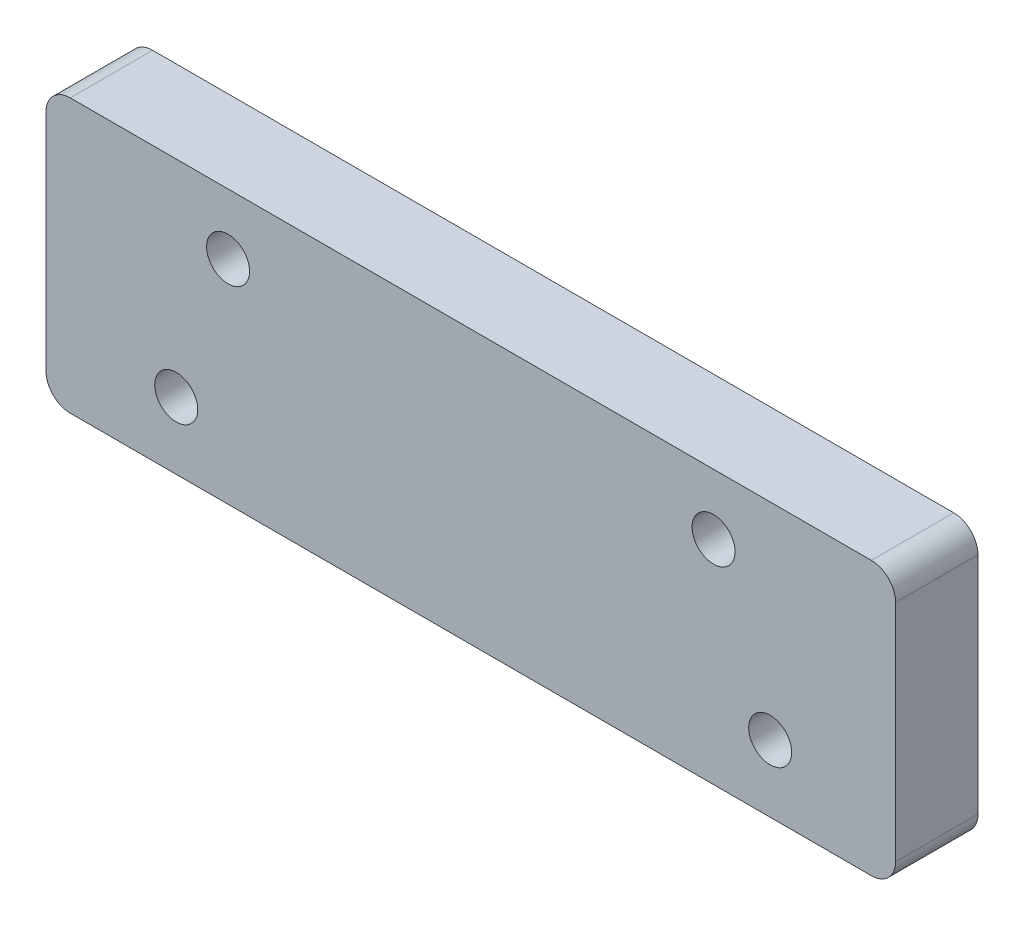
SolidWorks part; units mm, degrees
material "ABS"
ref_plane "X-Y Datum" through (0, 0, 0) normal (0, 0, 1) x (1, 0, 0)
ref_plane "X-Z Datum" through (0, 0, 0) normal (0, 1, 0) x (1, 0, 0)
ref_plane "Y-Z Datum" through (0, 0, 0) normal (1, 0, 0) x (0, 0, -1)
sketch "Sketch1" plane through (0, 0, 0) normal (0, 0, 1) x (1, 0, 0)
  line L0 (61.9, 0) -> (61.9, 14.5333) construction
  line L1 (106.35, 15.875) -> (17.45, 15.875)
  line L2 (106.35, 15.875) -> (106.35, 0)
  line L3 (106.35, 0) -> (17.45, 0)
  line L4 (17.45, 15.875) -> (17.45, 0)
  line L5 (106.35, 15.875) -> (17.45, 0) construction
  line L6 (106.35, 0) -> (17.45, 15.875) construction
  line L7 (87.225, 0) -> (36.575, 0) construction
  point P0 (61.9, 7.9375)
  point P9 (31.075, 7)
  point P13 (93.225, 7)
  dimension "D1" = 88.9
  dimension "D2" = 15.875
extrude "Boss-Extrude1" add sketch "Sketch1" against normal blind 7.62
hole_wizard "CBORE for M4 SHCS1" positions "Sketch2" profile "Sketch3" counterbore size "M4" standard "ANSI Metric" end condition through all
sketch "Sketch2" plane through (0, 0, -7.62) normal (0, 0, -1) x (-1, 0, 0)
  point P0 (-93.225, 7)
  point P3 (-31.075, 7)
sketch "Sketch3" plane through (93.225, 7, -7.62) normal (1, 0, 0) x (0, 1, 0)
  line L0 (0, 0) -> (0, 7.62)
  line L1 (0, 7.62) -> (2.25, 7.62)
  line L3 (2.25, 7.62) -> (2.25, 4)
  line L4 (2.25, 4) -> (4, 4)
  line L5 (4, 4) -> (4, 0)
  line L7 (4, 0) -> (0, 0)
  line L11 (0, -6.35) -> (0, 107.95) construction
  dimension "Thru Hole Dia." = 4.5
  dimension "Thru Hole Depth" = 7.62
  dimension "C'Bore Dia." = 8
  dimension "C'Bore Depth" = 4
sketch "Sketch4" plane through (0, 0, -7.62) normal (0, 0, -1) x (-1, 0, 0)
  line L4 (-17.45, 0) -> (-17.45, 15.875)
  line L5 (-17.45, 15.875) -> (-106.35, 15.875)
  line L6 (-106.35, 15.875) -> (-106.35, 0)
  line L7 (-106.35, 0) -> (-17.45, 0)
  line L8 (-17.45, 0) -> (-17.45, 15.875)
  line L9 (-17.45, 15.875) -> (-106.35, 15.875)
  line L10 (-106.35, 15.875) -> (-106.35, 0)
  line L11 (-106.35, 0) -> (-17.45, 0)
  circle A0 centre (-31.075, 7) radius 4 construction
  circle A1 centre (-93.225, 7) radius 4 construction
  circle A2 centre (-31.075, 7) radius 4
  circle A3 centre (-93.225, 7) radius 4
  dimension "D1" = 0
extrude "Boss-Extrude2" add sketch "Sketch4" along normal blind 1
sketch "Sketch5" plane through (0, 0, 0) normal (0, 0, 1) x (1, 0, 0)
  line L0 (106.35, 0) -> (106.35, 15.875) construction
  line L1 (17.45, 15.875) -> (106.35, 15.875)
  line L2 (17.45, 15.875) -> (17.45, 28.575)
  line L3 (17.45, 28.575) -> (106.35, 28.575)
  line L4 (106.35, 15.875) -> (106.35, 28.575)
  line L5 (17.45, 22.225) -> (106.35, 22.225) construction
  line L6 (61.9, 15.875) -> (61.9, 28.575) construction
  circle A0 centre (36.5, 22.225) radius 2
  circle A1 centre (87.3, 22.225) radius 2
  line M10 (106.35, 15.875) -> (17.45, 15.875)
  dimension "D2" = 4
  dimension "D1" = 12.7
  dimension "D3" = 25.4
extrude "Boss-Extrude3" add sketch "Sketch5" against normal blind 8.62 contours L4 L3 L2 A0 A1 M10 | A0 | A1 region at (61.9, 22.225, 0) region at (36.5, 22.225, 0) region at (87.3, 22.225, 0)
hole_wizard "M4 Clearance Hole1" positions "Sketch8" profile "Sketch9" hole size "M4" standard "ANSI Metric" end condition through all
sketch "Sketch8" plane through (0, 0, 0) normal (0, 0, 1) x (1, 0, 0)
  point P0 (36.5, 22.225)
  point P3 (87.3, 22.225)
sketch "Sketch9" plane through (36.5, 22.225, 0) normal (1, 0, 0) x (0, -1, 0)
  line L0 (0, 0) -> (0, 8.62)
  line L1 (0, 8.62) -> (2.25, 8.62)
  line L2 (2.25, 8.62) -> (2.25, 0)
  line L5 (2.25, 0) -> (0, 0)
  line L11 (0, -6.35) -> (0, 107.95) construction
  dimension "Thru Hole Dia." = 4.5
  dimension "Thru Hole Depth" = 8.62
fillet "Fillet1" radius 2.54 4 edges at (106.35, 28.575, -4.31) (106.35, 0, -4.31) (17.45, 0, -4.31) (17.45, 28.575, -4.31)
